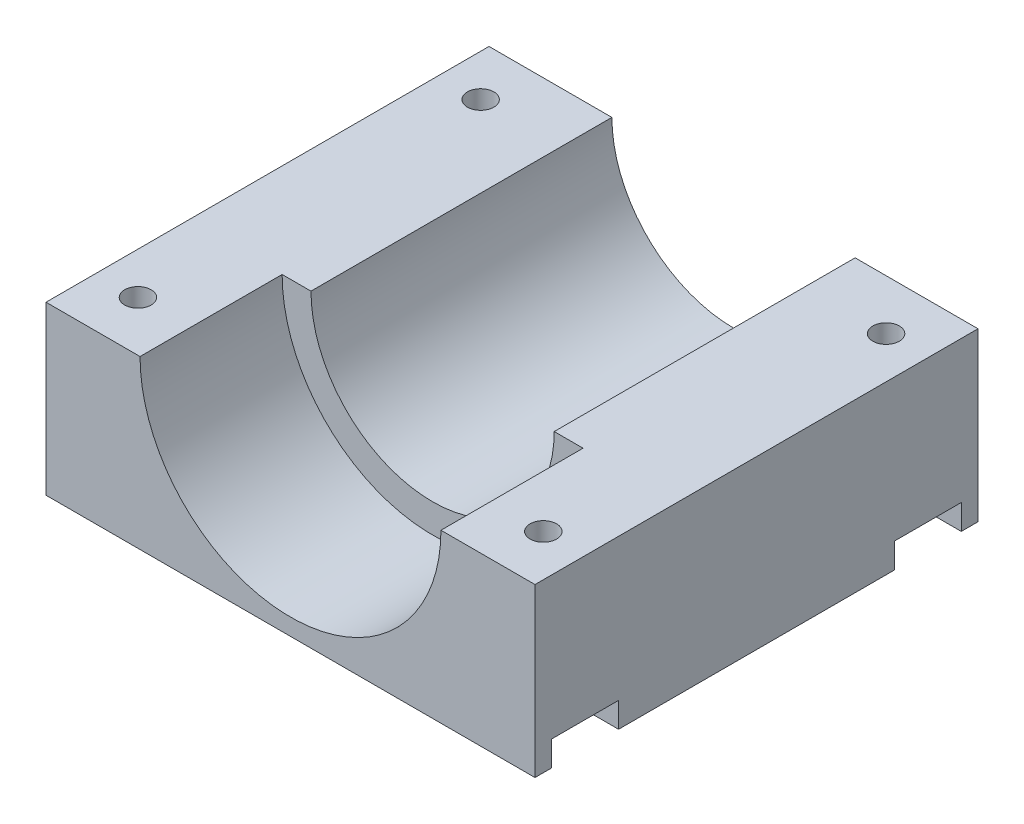
SolidWorks part; units mm, degrees
ref_plane "Alzado" through (0, 0, 0) normal (0, 0, 1) x (1, 0, 0)
ref_plane "Planta" through (0, 0, 0) normal (0, 1, 0) x (1, 0, 0)
ref_plane "Vista lateral" through (0, 0, 0) normal (1, 0, 0) x (0, 0, -1)
sketch "Sketch1" plane through (0, 0, 0) normal (0, 0, 1) x (1, 0, 0)
  line L1 (0, -13.6092) -> (58.5, -13.6092)
  line L2 (0, -13.6092) -> (0, 6.3908)
  line L3 (0, 6.3908) -> (58.5, 6.3908)
  line L4 (58.5, -13.6092) -> (58.5, 6.3908)
  dimension "D1" = 58.5
  dimension "D2" = 20
extrude "Boss-Extrude1" add sketch "Sketch1" along normal blind 53
sketch "Sketch3" plane through (0, 0, 53) normal (0, 0, 1) x (1, 0, 0)
  line L0 (11.25, 6.3908) -> (47.25, 6.3908)
  arc A0 (11.25, 6.3908) -> (47.25, 6.3908) centre (29.25, 6.3908) ccw
  dimension "D3" = 18
extrude "Cut-Extrude2" cut sketch "Sketch3" against normal blind 17
ref_plane "Plane1" through (11.25, 6.3908, 36) normal (-1, 0, 0) x (0, 0, 1)
sketch "Sketch5" plane through (0, 0, 0) normal (0, 0, -1) x (-1, 0, 0)
  line L4 (-43.8, 6.3908) -> (-14.7, 6.3908)
  arc A1 (-43.8, 6.3908) -> (-14.7, 6.3908) centre (-29.25, 6.3908) ccw
  dimension "D3" = 14.55
extrude "Cut-Extrude3" cut sketch "Sketch5" against normal blind 42.5
sketch "Sketch6" plane through (0, 0, 53) normal (0, 0, 1) x (1, 0, 0)
  line L0 (58.5, 2.6291) -> (49, 2.6291)
  line L1 (58.5, -13.6092) -> (58.5, 6.3908) construction
  line L2 (0, 2.6291) -> (9.5, 2.6291)
  line L3 (58.5, 2.6291) -> (58.5, -13.6092)
  line L4 (58.5, -13.6092) -> (0, -13.6092)
  line L5 (0, -13.6092) -> (0, 2.6291)
  arc A0 (49, 2.6291) -> (9.5, 2.6291) centre (29.25, 7.7188) cw
  dimension "D1" = 9.5
  dimension "D2" = 9.5
sketch "Sketch8" plane through (0, -13.6092, 0) normal (0, -1, 0) x (-1, 0, 0)
  line L0 (-58.5, -53) -> (-58.5, 0) construction
  line L1 (-58.5, -2) -> (-48.5, -2)
  line L2 (-58.5, -2) -> (-58.5, -10)
  line L3 (-58.5, -10) -> (-48.5, -10)
  line L4 (-48.5, -2) -> (-48.5, -10)
  line L5 (0, 0) -> (-58.5, 0) construction
  dimension "D1" = 8
  dimension "D2" = 2
  dimension "D4" = 0
extrude "Cut-Extrude6" cut sketch "Sketch8" against normal blind 3
sketch "Sketch7" plane through (0, -13.6092, 0) normal (0, -1, 0) x (-1, 0, 0)
  line L0 (-58.5, -53) -> (0, -53) construction
  line L1 (0, 0) -> (-58.5, 0) construction
  line L2 (-58.5, -2) -> (-58.5, -10) construction
  line L3 (0, -53) -> (0, 0) construction
  line L4 (-58.5, -53) -> (-58.5, -10) construction
  circle A0 centre (-53.5, -47) radius 1.585
  circle A1 centre (-53.5, -6) radius 1.585
  circle A2 centre (-5, -6) radius 1.585
  circle A3 centre (-5, -47) radius 1.585
  dimension "D1" = 3.17
  dimension "D2" = 3.17
  dimension "D3" = 3.17
  dimension "D4" = 3.17
  dimension "D5" = 6
  dimension "D6" = 6
  dimension "D7" = 6
  dimension "D8" = 6
  dimension "D9" = 5
  dimension "D10" = 5
  dimension "D11" = 5
  dimension "D12" = 5
extrude "Cut-Extrude5" cut sketch "Sketch7" against normal blind 92.5
ref_plane "Plane2" through (29.25, 0, 0) normal (-1, 0, 0) x (0, 0, 1)
ref_plane "Plane3" through (0, 0, 26.5) normal (0, 0, 1) x (1, 0, 0)
mirror "Mirror1" about plane through (0, 0, 26.5) normal (0, 0, 1) of "Cut-Extrude6" second plane through (29.25, 0, 0) second plane normal (-1, 0, 0)
